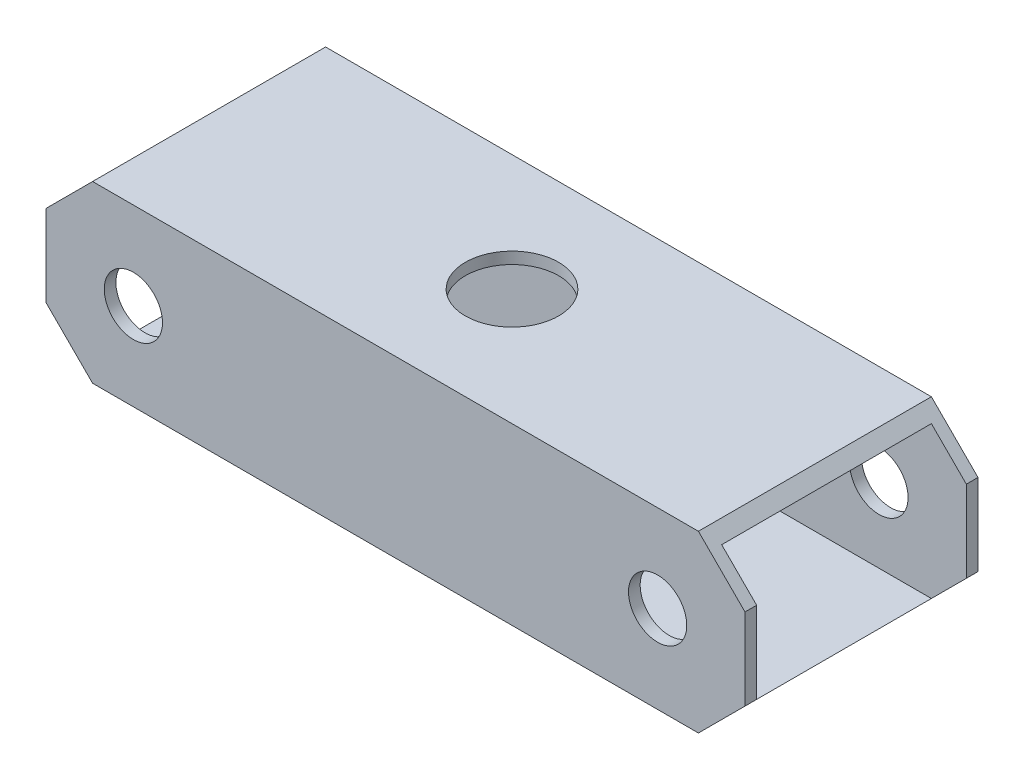
SolidWorks part; units mm, degrees
ref_plane "Front Plane" through (0, 0, 0) normal (0, 0, 1) x (1, 0, 0)
ref_plane "Top Plane" through (0, 0, 0) normal (0, 1, 0) x (1, 0, 0)
ref_plane "Right Plane" through (0, 0, 0) normal (1, 0, 0) x (0, 0, -1)
sketch "Sketch1" plane through (0, 0, 0) normal (0, 1, 0) x (1, 0, 0)
  line L1 (0, 0) -> (120, 0)
  line L2 (0, 0) -> (0, 40)
  line L3 (0, 40) -> (120, 40)
  line L4 (120, 0) -> (120, 40)
  dimension "D1" = 120
  dimension "D2" = 40
extrude "Boss-Extrude3" add sketch "Sketch1" along normal blind 30
sketch "Sketch3" plane through (0, 0, -40) normal (0, 0, -1) x (-1, 0, 0)
  line L0 (-120, 0) -> (0, 0) construction
  line L1 (-120, 30) -> (-120, 0) construction
  line L2 (-60, 30) -> (-60, 0) construction
  line L3 (-120, 30) -> (0, 30) construction
  circle A0 centre (-105, 15) radius 5
  circle A1 centre (-15, 15) radius 5
  dimension "D2" = 10
  dimension "D1" = 15
  dimension "D3" = 15
extrude "Cut-Extrude2" cut sketch "Sketch3" against normal through all
sketch3d "3DSketch1"
  line L0 (0, 28, -2) -> (0, 28, -38)
  line L1 (0, 28, -38) -> (0, 2, -38)
  line L2 (0, 2, -38) -> (0, 2, -2)
  line L3 (0, 2, -2) -> (0, 28, -2)
  line L4 (0, 28, -2) -> (0, 28, -38)
  line L5 (0, 28, -38) -> (0, 2, -38)
  line L6 (0, 2, -38) -> (0, 2, -2)
  line L7 (0, 2, -2) -> (0, 28, -2)
  dimension "D1" = 2
extrude "Cut-Extrude3" cut sketch "3DSketch1" along direction (-1, 0, 0) on the side against the normal blind 120
sketch "Sketch6" plane through (0, 30, 0) normal (0, 1, 0) x (1, 0, 0)
  line L0 (0, 0) -> (120, 0) construction
  line L1 (0, 40) -> (0, 0) construction
  circle A0 centre (60, 20) radius 8
  dimension "D1" = 16
  dimension "D2" = 20
  dimension "D3" = 60
extrude "Cut-Extrude4" cut sketch "Sketch6" against normal blind 120
chamfer "Chamfer2" distance 8 angle 45 4 edges at (0, 0, -20) (0, 30, -20) (120, 0, -20) (120, 30, -20)
